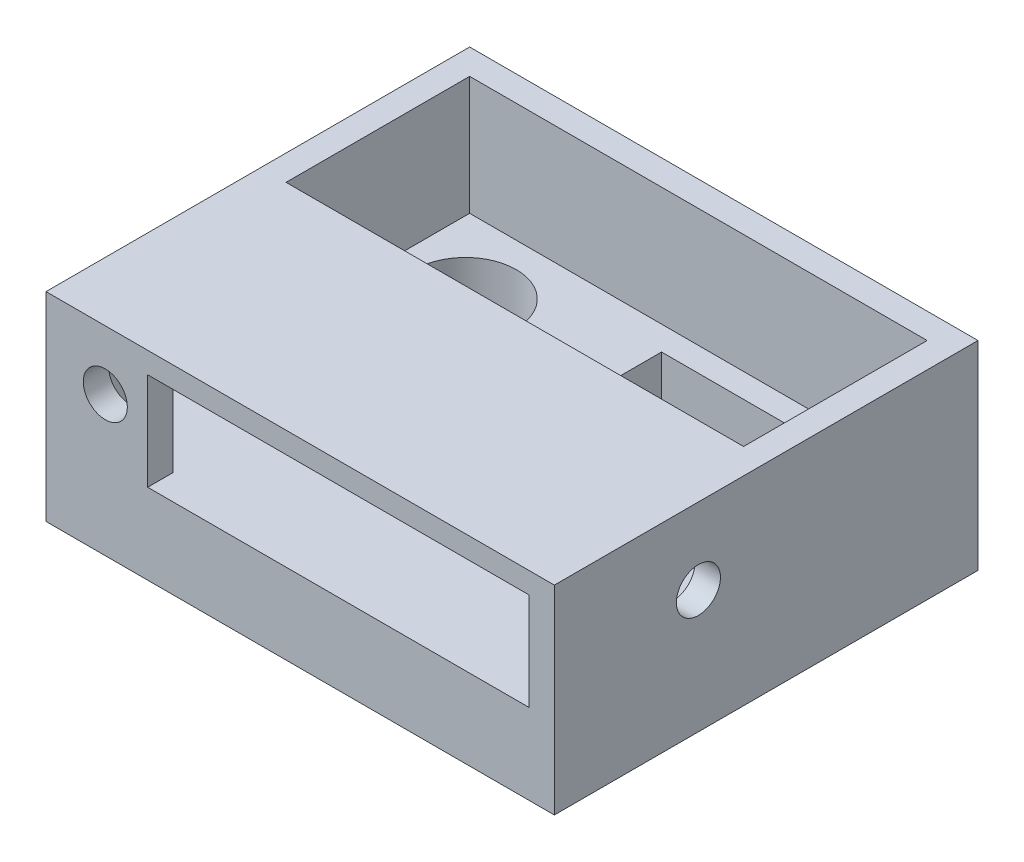
SolidWorks part; units mm, degrees
ref_plane "Plan de face" through (0, 0, 0) normal (0, 0, 1) x (1, 0, 0)
ref_plane "Plan de dessus" through (0, 0, 0) normal (0, 1, 0) x (1, 0, 0)
ref_plane "Plan de droite" through (0, 0, 0) normal (1, 0, 0) x (0, 0, -1)
sketch "Esquisse1" plane through (0, 0, 0) normal (0, 1, 0) x (1, 0, 0)
  line L1 (0, 0) -> (60, 0)
  line L2 (0, 0) -> (0, -50)
  line L3 (0, -50) -> (60, -50)
  line L4 (60, 0) -> (60, -50)
  dimension "D1" = 60
  dimension "D2" = 50
extrude "Boss.-Extru.1" add sketch "Esquisse1" along normal blind 21
sketch "Esquisse2" plane through (0, 21, 0) normal (0, 1, 0) x (1, 0, 0)
  line L0 (0, 0) -> (0, -50) construction
  line L1 (3, -3) -> (57, -3)
  line L2 (3, -3) -> (3, -47)
  line L3 (3, -47) -> (57, -47)
  line L4 (57, -3) -> (57, -47)
  line L5 (60, -50) -> (60, 0) construction
  line L6 (60, 0) -> (0, 0) construction
  line L7 (0, -50) -> (60, -50) construction
  dimension "D1" = 3
  dimension "D2" = 3
  dimension "D3" = 3
  dimension "D4" = 3
extrude "Enlèv. mat.-Extru.1" cut sketch "Esquisse2" against normal blind 14
sketch "Esquisse3" plane through (0, 7, 0) normal (0, 1, 0) x (1, 0, 0)
  line L0 (3, -25) -> (57, -25) construction
  line L1 (28.5, -5.85) -> (51.5, -5.85)
  line L2 (28.5, -5.85) -> (28.5, -18.15)
  line L3 (28.5, -18.15) -> (51.5, -18.15)
  line L4 (51.5, -5.85) -> (51.5, -18.15)
  line L5 (3, -3) -> (3, -47) construction
  line L6 (57, -47) -> (57, -3) construction
  line L7 (30, -3) -> (30, -47) construction
  line L8 (57, -3) -> (3, -3) construction
  line L9 (3, -47) -> (57, -47) construction
  line L10 (28.5, -12) -> (51.5, -12) construction
  line L11 (40, -5.85) -> (40, -18.15) construction
  dimension "D1" = 10
  dimension "D2" = 23
  dimension "D3" = 12.3
  dimension "D4" = 13
extrude "Enlèv. mat.-Extru.2" cut sketch "Esquisse3" against normal up to next
sketch "Esquisse4" plane through (60, 0, 0) normal (1, 0, 0) x (0, 0, -1)
  line L0 (-50, 10.5) -> (0, 10.5) construction
  line L1 (-50, 21) -> (-50, 0) construction
  line L2 (0, 21) -> (0, 0) construction
  line L3 (-25, 21) -> (-25, 0) construction
  line L4 (-50, 21) -> (0, 21) construction
  line L5 (-50, 0) -> (0, 0) construction
  circle A0 centre (-33, 12) radius 2.6
  dimension "D1" = 5.2
  dimension "D2" = 1.5
  dimension "D3" = 8
extrude "Enlèv. mat.-Extru.3" cut sketch "Esquisse4" against normal blind 10
sketch "Esquisse5" plane through (0, 0, 0) normal (0, -1, 0) x (1, 0, 0)
  line L0 (28.5, 5.85) -> (51.5, 5.85) construction
  line L1 (60, 0) -> (0, 0)
  line L2 (60, 0) -> (60, 50)
  line L3 (60, 50) -> (0, 50)
  line L4 (0, 0) -> (0, 50)
  line L5 (56.5, 5.85) -> (23.5, 5.85)
  line L6 (56.5, 5.85) -> (56.5, 18.15)
  line L7 (56.5, 18.15) -> (23.5, 18.15)
  line L8 (23.5, 5.85) -> (23.5, 18.15)
  line L9 (51.5, 18.15) -> (28.5, 18.15) construction
  line L10 (51.5, 5.85) -> (51.5, 18.15) construction
  line L11 (28.5, 18.15) -> (28.5, 5.85) construction
  dimension "D1" = 5
  dimension "D2" = 5
extrude "Boss.-Extru.2" add sketch "Esquisse5" along normal blind 2.5
sketch "Esquisse6" plane through (0, 0, 50) normal (0, 0, 1) x (1, 0, 0)
  line L0 (0, 21) -> (60, 21) construction
  line L2 (0, 21) -> (0, -2.5) construction
  circle A0 centre (7, 14) radius 2.6
  dimension "D1" = 5.2
  dimension "D3" = 7
  dimension "D2" = 7
extrude "Enlèv. mat.-Extru.4" cut sketch "Esquisse6" against normal blind 10
sketch "Esquisse8" plane through (0, 21, 0) normal (0, 1, 0) x (1, 0, 0)
  line L0 (0, -50) -> (60, -50) construction
  line L1 (0, -50) -> (60, -50)
  line L2 (0, -50) -> (0, -24.6679)
  line L3 (0, -24.6679) -> (60, -24.6679)
  line L4 (60, -50) -> (60, -24.6679)
  line L5 (60, -50) -> (60, 0) construction
extrude "Boss.-Extru.3" add sketch "Esquisse8" against normal blind 2.5
sketch "Esquisse9" plane through (0, 0, 50) normal (0, 0, 1) x (1, 0, 0)
  line L1 (57, 18.5) -> (12, 18.5)
  line L2 (57, 18.5) -> (57, 7)
  line L3 (57, 7) -> (12, 7)
  line L4 (12, 18.5) -> (12, 7)
  line L5 (0, 21) -> (60, 21) construction
  line L6 (60, 21) -> (60, -2.5) construction
  line L11 (3, 7) -> (57, 7) construction
  dimension "D1" = 2.5
  dimension "D2" = 45
  dimension "D3" = 3
extrude "Enlèv. mat.-Extru.6" cut sketch "Esquisse9" against normal blind 3
sketch "Esquisse10" plane through (0, -2.5, 0) normal (0, -1, 0) x (-1, 0, 0)
  line L0 (-23.5, -12) -> (6.0842, -12) construction
  line L1 (-23.5, -18.15) -> (-23.5, -5.85) construction
  circle A0 centre (-11.5, -12) radius 6
  dimension "D2" = 12
  dimension "D1" = 12
extrude "Enlèv. mat.-Extru.7" cut sketch "Esquisse10" against normal up to surface (9.5 mm away) up to face at (40, 7, 12)
